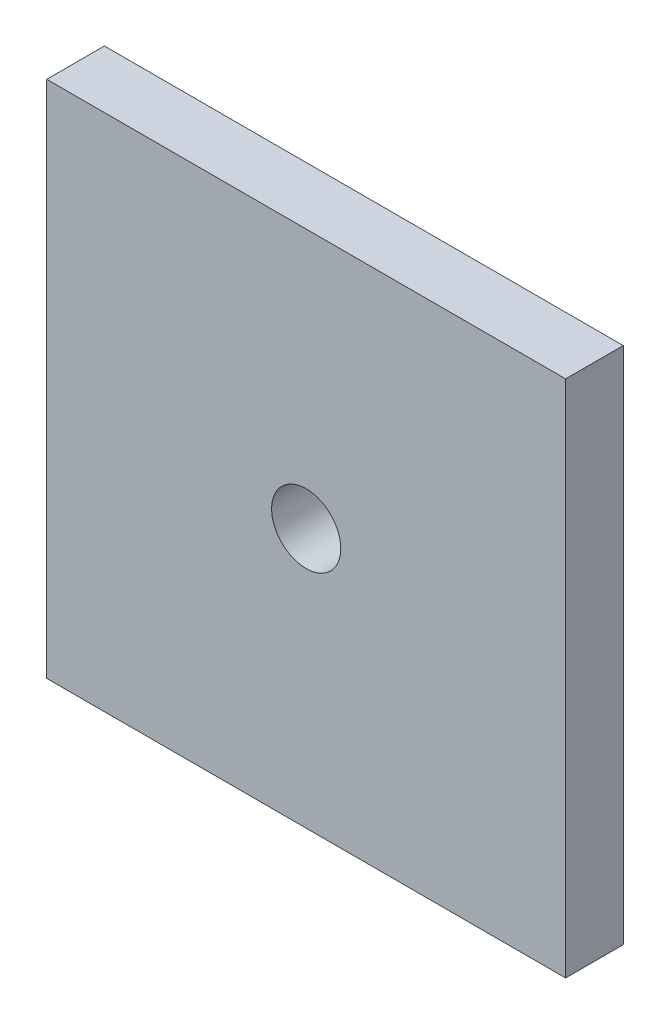
SolidWorks part; units mm, degrees
material "7075-O (SS)"
ref_plane "Front Plane" through (0, 0, 0) normal (0, 0, 1) x (1, 0, 0)
ref_plane "Top Plane" through (0, 0, 0) normal (0, 1, 0) x (1, 0, 0)
ref_plane "Right Plane" through (0, 0, 0) normal (1, 0, 0) x (0, 0, -1)
sketch "Sketch1" plane through (0, 0, 0) normal (0, 0, 1) x (1, 0, 0)
  line L1 (-22.5, -22.5) -> (22.5, -22.5)
  line L2 (-22.5, -22.5) -> (-22.5, 22.5)
  line L3 (-22.5, 22.5) -> (22.5, 22.5)
  line L4 (22.5, -22.5) -> (22.5, 22.5)
  line L5 (-22.5, -22.5) -> (22.5, 22.5) construction
  line L6 (-22.5, 22.5) -> (22.5, -22.5) construction
  circle A0 centre (0, 0) radius 3
  point P0 (0, 0)
  dimension "D3" = 6
  dimension "D1" = 45
  dimension "D2" = 45
extrude "Boss-Extrude1" add sketch "Sketch1" along normal blind 5
